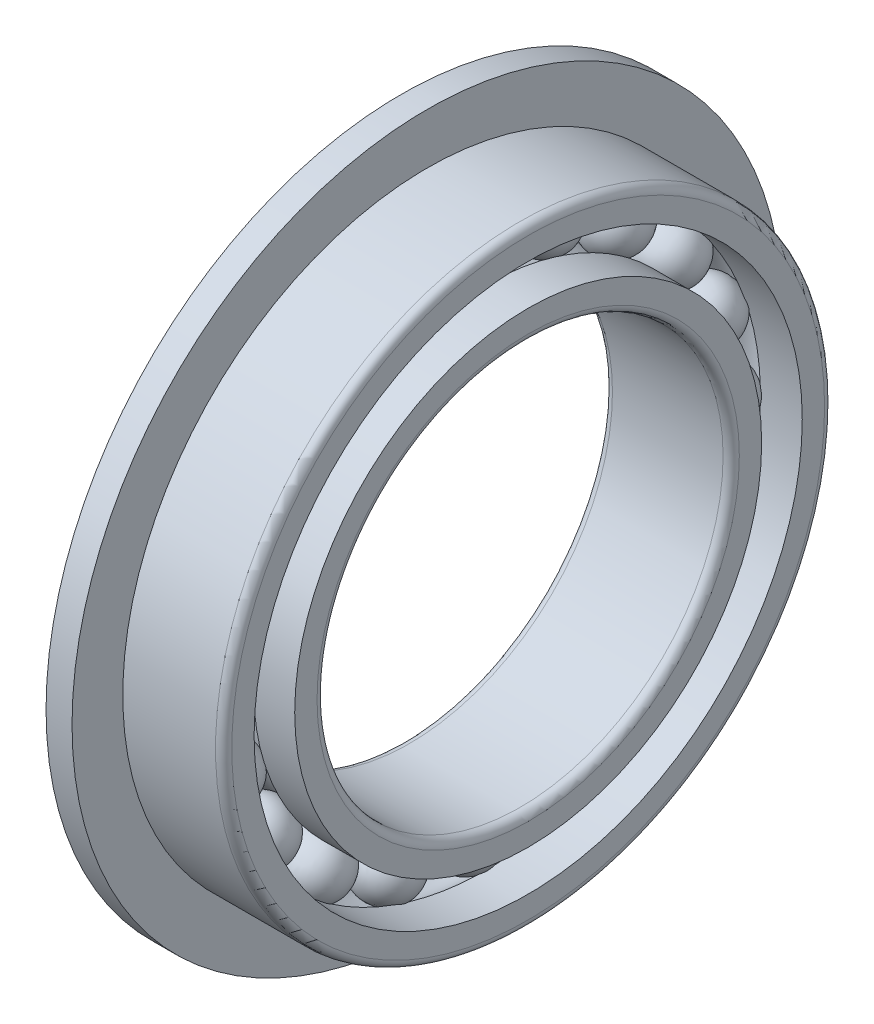
SolidWorks part; units mm, degrees
material "AISI 316 Stainless Steel Sheet (SS)"
ref_plane "Plane1" through (0, 0, 0) normal (0, 0, 1) x (1, 0, 0)
ref_plane "Plane2" through (0, 0, 0) normal (0, 1, 0) x (1, 0, 0)
ref_plane "Plane3" through (0, 0, 0) normal (1, 0, 0) x (0, 0, -1)
sketch "Clipboard" plane through (0, 0, 0) normal (0, 0, 1) x (1, 0, 0)
  line L0 (-10, 0) -> (10, 0) construction
  line L1 (0, 0) -> (21.0122, -7.6478)
  line L2 (0, 0) -> (7.4588, 2.7148)
  line L3 (0, 0) -> (21.0122, -7.6478)
  line L4 (0, 0) -> (-22.3573, -0.3902)
  dimension "BallCLRad" = 7.9375
  dimension "Count" = 20
  dimension "Show_count" = 20
  dimension "Max_count" = 20
  dimension "Min_count" = 1
sketch "CagSpiSke" plane through (0, 0, 0) normal (0, 0, 1) x (1, 0, 0)
  line L0 (0.0952, 7.7787) -> (0.0953, 8.0962)
  line L1 (0.0953, 8.0962) -> (-0.0953, 8.0962)
  line L2 (-0.0953, 8.0962) -> (-0.0952, 7.7787)
  line L3 (-0.0952, 7.7787) -> (0.0952, 7.7787)
  line L4 (-20.6375, 0) -> (20.6375, 0) construction
  line L5 (0, 0) -> (0, 23.7692) construction
  dimension "Thickness" = 0.1905
  dimension "OD" = 16.1925
  dimension "ID" = 15.5575
revolve "CageSpine" add sketch "CagSpiSke" angle 0.001 about L4 reverse direction yes
ref_axis "Axis1" through (-50, 0, 0) along (1, 0, 0)
sketch "CagBalSke" plane through (0, 0, 0) normal (0, 0, 1) x (1, 0, 0)
  line L0 (-1.0478, 7.9375) -> (1.0478, 7.9375)
  line L1 (-1.905, 7.9375) -> (1.905, 7.9375) construction
  line L2 (-10, 0) -> (10, 0) construction
  line L3 (0, 0) -> (0, 24) construction
  arc A0 (1.0478, 7.9375) -> (-1.0478, 7.9375) centre (0, 7.9375) cw
  dimension "CageWallOD" = 2.0955
  dimension "BallCLRad" = 7.9375
revolve "CageBall" [suppressed] add sketch "CagBalSke" angle 360 about L1 reverse direction yes
pattern_circular "CageBalls" [suppressed] count 20 every 18 about axis through (-50, 0, 0) along (1, 0, 0)
sketch "CagTrmODSke" plane through (0, 0, 0) normal (0, 0, 1) x (1, 0, 0)
  line L0 (1.0732, 8.0962) -> (1.0732, 9.0107)
  line L1 (1.0732, 9.0107) -> (-1.0732, 9.0107)
  line L2 (-1.0732, 9.0107) -> (-1.0732, 8.0962)
  line L3 (-1.0732, 8.0962) -> (1.0732, 8.0962)
  line L4 (-20.6375, 0) -> (20.6375, 0) construction
  line L5 (0, 0) -> (0, 25) construction
  dimension "Width" = 2.1463
  dimension "ID" = 16.1925
  dimension "OD" = 18.0213
revolve "CageTrimOD" [suppressed] cut sketch "CagTrmODSke" angle 360 about L4 reverse direction yes
sketch "CagTrmIDSke" plane through (0, 0, 0) normal (0, 0, 1) x (1, 0, 0)
  line L0 (1.0732, 6.9151) -> (1.0732, 7.7787)
  line L1 (1.0732, 7.7787) -> (-1.0732, 7.7787)
  line L2 (-1.0732, 7.7787) -> (-1.0732, 6.9151)
  line L3 (-1.0732, 6.9151) -> (1.0732, 6.9151)
  line L4 (-20.6375, 0) -> (20.6375, 0) construction
  line L5 (0, 0) -> (0, 25) construction
  dimension "ID" = 13.8303
  dimension "OD" = 15.5575
  dimension "Width" = 2.1463
revolve "CageTrimID" [suppressed] cut sketch "CagTrmIDSke" angle 360 about L4 reverse direction yes
sketch "BalSimSke" plane through (0, 0, 0) normal (0, 0, 1) x (1, 0, 0)
  line L0 (-10, 0) -> (10, 0) construction
  line L1 (-10, 7.9375) -> (10, 7.9375) construction
  line L2 (0, 0) -> (0, 23) construction
  circle A0 centre (0, 7.9375) radius 0.9525
  dimension "Ball_diameter" = 1.905
  dimension "BallCLRad" = 7.9375
revolve "BallsSimplified" [suppressed] add sketch "BalSimSke" angle 360 about L0
sketch "BalDetSke" plane through (0, 0, 0) normal (0, 0, 1) x (1, 0, 0)
  line L0 (-0.9525, 7.9375) -> (0.9525, 7.9375)
  line L1 (-1.905, 7.9375) -> (1.905, 7.9375) construction
  line L2 (0, 0) -> (0, 25) construction
  arc A0 (0.9525, 7.9375) -> (-0.9525, 7.9375) centre (0, 7.9375) cw
  dimension "Ball_diameter" = 1.905
  dimension "BallCLRad" = 7.9375
revolve "BallDetailed" add sketch "BalDetSke" angle 360 about L1 reverse direction yes
sketch "InnRacSke" plane through (0, 0, 0) normal (0, 0, 1) x (1, 0, 0)
  line L0 (-0.6501, 7.3025) -> (-1.9837, 7.3025)
  line L1 (-1.9837, 7.3025) -> (-1.9837, 6.604)
  line L2 (-1.7297, 6.35) -> (1.7297, 6.35)
  line L3 (1.9837, 6.604) -> (1.9837, 7.3025)
  line L4 (1.9837, 7.3025) -> (0.7009, 7.3025)
  line L5 (-20.6375, 0) -> (20.6375, 0) construction
  line L6 (0, 0) -> (0, 30) construction
  arc A0 (-1.9837, 6.604) -> (-1.7297, 6.35) centre (-1.7297, 6.604) ccw
  arc A1 (1.7297, 6.35) -> (1.9837, 6.604) centre (1.7297, 6.604) ccw
  arc A2 (0.7009, 7.3025) -> (-0.6501, 7.3025) centre (0.0254, 7.9375) cw
  dimension "Fillet_radius" = 0.254
  dimension "Ball_diameter" = 1.8542
  dimension "ID" = 12.7
  dimension "OD" = 14.605
  dimension "Width" = 3.9675
  dimension "BallCLRad" = 7.9375
  dimension "Skew" = 0.0254
revolve "InnerRace" add sketch "InnRacSke" angle 360 about L5 reverse direction yes
sketch "OutRacSke" plane through (0, 0, 0) normal (0, 0, 1) x (1, 0, 0)
  line L0 (-0.6755, 8.5725) -> (-1.9837, 8.5725)
  line L1 (-1.9837, 8.5725) -> (-1.9837, 9.271)
  line L2 (-1.7297, 9.525) -> (1.7297, 9.525)
  line L3 (1.9837, 9.271) -> (1.9837, 8.5725)
  line L4 (1.9837, 8.5725) -> (0.6755, 8.5725)
  line L5 (-20.6375, 0) -> (20.6375, 0) construction
  line L6 (0, 0) -> (0, 30) construction
  arc A0 (-1.9837, 9.271) -> (-1.7297, 9.525) centre (-1.7297, 9.271) cw
  arc A1 (1.7297, 9.525) -> (1.9837, 9.271) centre (1.7297, 9.271) cw
  arc A2 (0.6755, 8.5725) -> (-0.6755, 8.5725) centre (0, 7.9375) ccw
  dimension "Fillet_radius" = 0.254
  dimension "Ball_diameter" = 1.8542
  dimension "OD" = 19.05
  dimension "ID" = 17.145
  dimension "Width" = 3.9675
  dimension "BallCLRad" = 7.9375
revolve "OuterRace" add sketch "OutRacSke" angle 360 about L5 reverse direction yes
pattern_circular "BallsDetailed" count 20 every 18 about axis through (-50, 0, 0) along (1, 0, 0) of "BallDetailed"
sketch "Sketch1" plane through (0, 0, 0) normal (0, 0, 1) x (1, 0, 0)
  line L0 (0, 0) -> (-7.5958, 0) construction
  line L2 (-1.9837, 9.271) -> (-1.1709, 9.271)
  line L3 (-1.9837, 9.271) -> (-1.9837, 11.1125)
  line L4 (-1.9837, 11.1125) -> (-1.1709, 11.1125)
  line L5 (-1.1709, 9.271) -> (-1.1709, 11.1125)
  dimension "D1" = 11.1125
  dimension "D2" = 0.8128
revolve "Revolve1" add sketch "Sketch1" angle 360 about L0
equation "\"BallCLRad@Clipboard\" = ( \"OD@OutRacSke\" + \"ID@InnRacSke\" ) / 4"
equation "\"BallCLRad@BalSimSke\" = \"BallCLRad@Clipboard\""
equation "\"BallCLRad@BalDetSke\" = \"BallCLRad@Clipboard\""
equation "\"BallCLRad@InnRacSke\" = \"BallCLRad@Clipboard\""
equation "\"BallCLRad@OutRacSke\" = \"BallCLRad@Clipboard\""
equation "\"Ball_diameter@InnRacSke\" = \"Ball_diameter@BalDetSke\" - 0.002"
equation "\"Ball_diameter@OutRacSke\" = \"Ball_diameter@BalDetSke\" - 0.002"
equation "\"Ball_diameter@BalSimSke\" = \"Ball_diameter@BalDetSke\""
equation "\"Width@OutRacSke\" = \"Width@InnRacSke\""
equation "\"Fillet_radius@OutRacSke\" = \"Fillet_radius@InnRacSke\""
equation "\"Max_count@Clipboard\" = int( 3.14159265 / atn(( \"Ball_diameter@BalDetSke\" / 2) / sqr( \"BallCLRad@Clipboard\"  *  \"BallCLRad@Clipboard\" - ( \"Ball_diameter@BalDetSke\" / 2) *  ( \"Ball_diameter@BalDetSke\" / 2))))"
equation "\"Max_count@Clipboard\" = ((sgn( \"Max_count@Clipboard\" - \"Count@Clipboard\" )-1)*( \"Max_count@Clipboard\" - \"Count@Clipboard\" ))/-2+ \"Count@Clipboard\""
equation "\"Count@BallsDetailed\" = int( \"Show_count@Clipboard\" ) "
equation "\"Count@BallsDetailed\" = ((sgn( \"Count@BallsDetailed\" - \"Max_count@Clipboard\" )-1)*( \"Count@BallsDetailed\" - \"Max_count@Clipboard\" ))/-2+ \"Max_count@Clipboard\""
equation "\"Count@BallsDetailed\" = ((sgn( \"Count@BallsDetailed\" - \"Min_count@Clipboard\" )+1)*( \"Count@BallsDetailed\" - \"Min_count@Clipboard\"))/2 +\"Min_count@Clipboard\""
equation "\"Angle@BallsDetailed\" = 360.0 / \"Max_count@Clipboard\""
equation "\"BallCLRad@CagBalSke\" = \"BallCLRad@Clipboard\""
equation "\"Count@CageBalls\" = \"Count@BallsDetailed\""
equation "\"Angle@CageBalls\" = \"Angle@BallsDetailed\""
equation "\"Angle@CageSpine\" =  \"Angle@CageBalls\" * ( \"Count@CageBalls\" -1 + int( \"Count@CageBalls\" / \"Max_count@Clipboard\" ) )  + 0.001 -  int( \"Count@CageBalls\" / \"Max_count@Clipboard\" ) * 0.001"
equation "\"Angle@CageSpine\" =  \"Angle@CageSpine\" * int( \"Min_count@Clipboard\" / 2) + int(1 / \"Min_count@Clipboard\")  * 0.001"
equation "\"CageWallOD@CagBalSke\" =  \"Ball_diameter@BalDetSke\" * 1.1"
equation "\"Thickness@CagSpiSke\" =  \"Ball_diameter@BalDetSke\" * 0.1"
equation "\"OD@CagTrmODSke\" = \"BallCLRad@Clipboard\" * 2 + \"CageWallOD@CagBalSke\" + 0.002"
equation "\"ID@CagTrmODSke\" = \"BallCLRad@Clipboard\" * 2 + \"Ball_diameter@BalDetSke\" / 6"
equation "\"OD@CagTrmIDSke\" = \"BallCLRad@Clipboard\" * 2 - \"Ball_diameter@BalDetSke\" / 6"
equation "\"ID@CagTrmIDSke\" = \"BallCLRad@Clipboard\" * 2 - \"CageWallOD@CagBalSke\" + 0.002"
equation "\"OD@CagSpiSke\" = \"ID@CagTrmODSke\""
equation "\"ID@CagSpiSke\" = \"OD@CagTrmIDSke\""
equation "\"Width@CagTrmODSke\" = \"CageWallOD@CagBalSke\" + 0.002"
equation "\"Width@CagTrmIDSke\" = \"CageWallOD@CagBalSke\" + 0.002"
